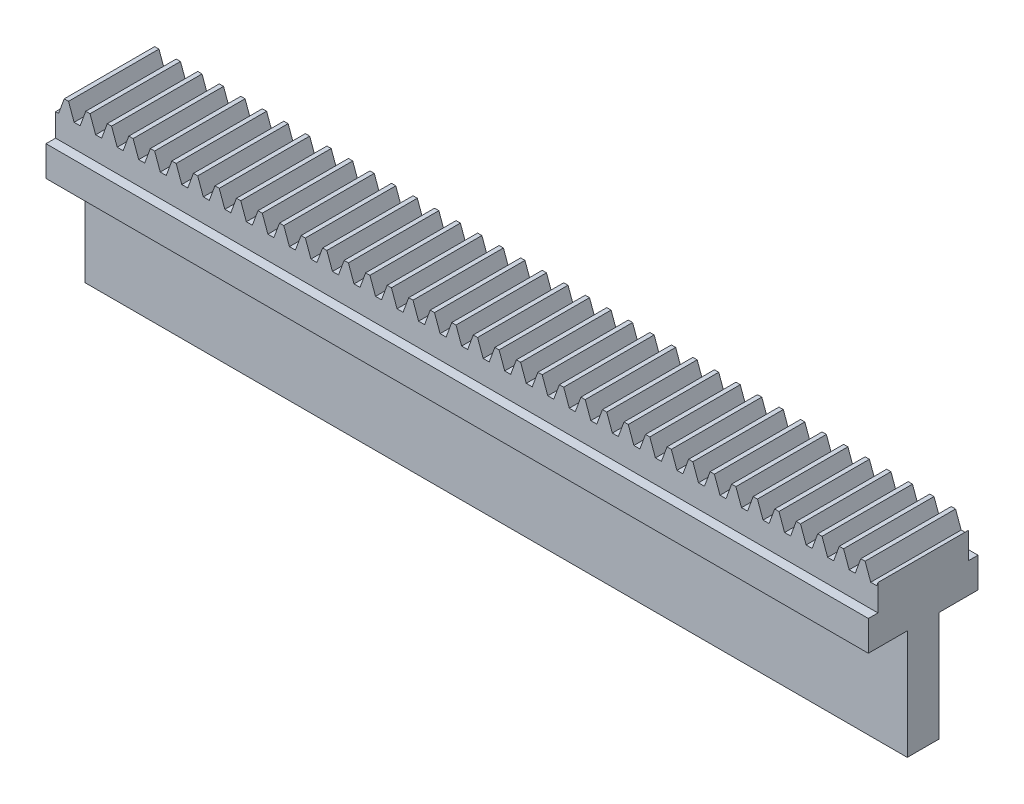
SolidWorks part; units mm, degrees
extrude "Blank" add sketch "BlankSke" against normal blind 20
sketch "BlankSke" plane through (0, 0, 0) normal (0, 0, 1) x (1, 0, 0)
  line L1 (0, 0) -> (150, 0)
  line L2 (0, 0) -> (0, 12.5)
  line L3 (0, 12.5) -> (150, 12.5)
  line L4 (150, 0) -> (150, 12.5)
  dimension "Length" = 150
ref_plane "Plane1" through (0, 0, 0) normal (0, 0, 1) x (1, 0, 0)
ref_plane "Plane2" through (0, 0, 0) normal (0, 1, 0) x (1, 0, 0)
ref_plane "Plane3" through (0, 0, 0) normal (1, 0, 0) x (0, 0, -1)
other "Configuration Table"
sketch "HoldingSke" plane through (0, 0, 0) normal (0, 1, 0) x (1, 0, 0)
  line L0 (0, 0) -> (0.1113, 0.7922)
  line L1 (-15, 0) -> (100, 0) construction
  line L2 (0, 0) -> (-2.1039, 2.3779)
  line L3 (0, 0) -> (-11.863, 4.5341)
  line L4 (0, 0) -> (6.6156, 5.5511)
  line L5 (0, 0) -> (-23.7986, -8.8762)
  line L6 (0, 0) -> (-10.5278, -7.1032)
  line L9 (-71.009, 38.7566) -> (69.9449, 90.0596)
  line L10 (-76.2, 3.6279) -> (-64.95, 3.6279)
  line L11 (0, 0) -> (-7, 0)
  line L12 (-76.2, 101.6) -> (-76.155, 101.6)
  line L13 (24.9733, 27.94) -> (52.9518, 28.4284)
  line L14 (24.9733, 27.94) -> (24.9743, 27.94)
  line L15 (24.9733, 27.94) -> (100.4006, 29.5858)
  circle A0 centre (0, 0) radius 19.05
  circle A1 centre (0, 0) radius 5.625
  circle A2 centre (0, 0) radius 12.7
  dimension "Num_teeth" = 40
  dimension "Width" = 7
  dimension "Length" = 150
  dimension "Pitch_height" = 11.25
sketch "TooCutSkeIll" plane through (0, 0, 0) normal (0, 0, 1) x (1, 0, 0)
  line L0 (-1.5597, 12.4671) -> (-0.6231, 9.8938)
  line L1 (-0.3285, 9.6875) -> (0.3285, 9.6875)
  line L2 (0.6231, 9.8938) -> (1.5597, 12.4671)
  line L3 (150, 12.5) -> (0, 12.5) construction
  line L4 (0, 0) -> (0, 64.897) construction
  line L5 (-13.208, 11.25) -> (12.954, 11.25) construction
  line L6 (0, 0) -> (150, 0) construction
  line L7 (1.1167, 11.25) -> (1.1167, 48.7463) construction
  line L8 (-1.1167, 11.25) -> (-1.1167, 48.7463) construction
  line L9 (1.6067, 12.5) -> (1.6067, 12.5254)
  line L10 (-1.6067, 12.5) -> (-1.6067, 12.5254)
  line L11 (-1.6067, 12.5254) -> (1.6067, 12.5254)
  arc A0 (0.3285, 9.6875) -> (0.6231, 9.8938) centre (0.3285, 10.001) ccw
  arc A1 (-0.6231, 9.8938) -> (-0.3285, 9.6875) centre (-0.3285, 10.001) ccw
  arc A2 (1.6067, 12.5) -> (1.5597, 12.4671) centre (1.6067, 12.45) ccw
  arc A3 (-1.5597, 12.4671) -> (-1.6067, 12.5) centre (-1.6067, 12.45) ccw
  dimension "Addendum_plus" = 1.2754
  dimension "Pitch_height" = 11.25
  dimension "Pressure_angle" = 20
  dimension "Gap_width" = 2.2335
  dimension "Dedendum" = 1.5625
extrude "ToothCutIll" [suppressed] cut sketch "TooCutSkeIll" against normal through all
sketch "TooCutSkeSim" plane through (0, 0, 0) normal (0, 0, 1) x (1, 0, 0)
  line L0 (0.548, 9.6875) -> (-0.548, 9.6875)
  line L1 (1.581, 12.5254) -> (0.548, 9.6875)
  line L2 (0, 17.4625) -> (0, 53.467) construction
  line L3 (1.581, 12.5254) -> (-1.581, 12.5254)
  line L6 (-1.581, 12.5254) -> (-0.548, 9.6875)
  line L9 (-1.1167, 11.25) -> (1.1167, 11.25) construction
  line L10 (0, 0) -> (150, 0) construction
  line L11 (1.1167, 11.25) -> (1.1167, 53.467) construction
  line L12 (-1.1167, 11.25) -> (-1.1167, 53.467) construction
  dimension "Addendum_plus" = 1.2754
  dimension "Pitch_height" = 11.25
  dimension "Pressure_angle" = 20
  dimension "Gap_width" = 2.2335
  dimension "Dedendum" = 1.5625
extrude "ToothCutSim" cut sketch "TooCutSkeSim" against normal through all
pattern_linear "TeethCuts" count 40 spacing 3.927 along (1, 0, 0) of "ToothCutIll", "ToothCutSim"
sketch "Croquis3" plane through (0, 0, 0) normal (0, 0, 1) x (1, 0, 0)
  line L0 (0, 9.6875) -> (0, 0) construction
  line L1 (0, 5.5) -> (150.5773, 5.5)
  line L2 (0, 5.5) -> (0, 12.8527)
  line L3 (0, 12.8527) -> (150.5773, 12.8527)
  line L4 (150.5773, 5.5) -> (150.5773, 12.8527)
  line L5 (123.408, 0) -> (123.408, 5.5) construction
  line L6 (0, 0) -> (150, 0) construction
  dimension "D1" = 5.5
extrude "Cortar-Extruir1" cut sketch "Croquis3" against normal blind 1.75
sketch "Croquis4" plane through (0, 0, -20) normal (0, 0, -1) x (-1, 0, 0)
  line L0 (-150, 0) -> (-150, 10.3093) construction
  line L1 (-150, 5.5) -> (0, 5.5)
  line L2 (-150, 5.5) -> (-150, 14.4015)
  line L3 (-150, 14.4015) -> (0, 14.4015)
  line L4 (0, 5.5) -> (0, 14.4015)
  line L5 (0, 0) -> (-150, 0) construction
  dimension "D1" = 5.5
extrude "Cortar-Extruir2" cut sketch "Croquis4" against normal blind 1.75
sketch "Croquis5" plane through (150, 0, 0) normal (1, 0, 0) x (0, 0, -1)
  line L0 (0, 0) -> (18.25, 10.3093) construction
  line L1 (18.25, 10.3093) -> (1.75, 10.3093) construction
  line L2 (1.75, 10.3093) -> (20, 0) construction
  circle A0 centre (10, 5.6489) radius 2
  dimension "D1" = 4
sketch "Croquis6" plane through (0, 0, 0) normal (0, -1, 0) x (1, 0, 0)
  line L6 (0, -20) -> (0, 0) construction
  line L8 (0, -7.1) -> (150, -7.1)
  line L9 (0, -7.1) -> (0, -12.9)
  line L11 (0, -12.9) -> (150, -12.9)
  line L12 (150, -7.1) -> (150, -12.9)
  line L13 (150, -20) -> (150, 0) construction
  line L14 (25.8218, 0) -> (25.8218, -7.1) construction
  line L15 (0, 0) -> (150, 0) construction
  line L16 (25.8218, -7.1) -> (32.7674, -12.9) construction
  line L17 (32.7674, -12.9) -> (32.7674, -20) construction
  line L18 (0, -20) -> (150, -20) construction
  dimension "D1" = 5.8
extrude "Saliente-Extruir1" add sketch "Croquis6" along normal blind 20
equation "' \"Module@HoldingSke\" = 6.35"
equation "' \"Num_teeth@HoldingSke\" = 12"
equation "' \"Ap@HoldingSke\" =  20"
equation "' \"Ap@HoldingSke\" = 20"
equation "' \"Width@HoldingSke\" = 0.25 * 25.4"
equation "' \"Show_teeth@HoldingSke\" = 500"
equation "' \"Backlash@HoldingSke\" = 0.009 * 25.4"
equation "' \"Addendum_fac@HoldingSke\" = 1.0"
equation "' \"Dedendum_fac@HoldingSke\" = 1.25"
equation "' \"Dedendum_add@HoldingSke\" = 0.00005 * 25.4"
equation "' \"Clearance_fac@HoldingSke\" = 0.25"
equation "' \"Pitch_height@HoldingSke\" = 1 * 25.4"
equation "' \"Length@HoldingSke\" = 4.71 * 25.4"
equation "\"Pitch@HoldingSke\" = 1 / \"Module@HoldingSke\""
equation "\"MPH@HoldingSke\" = \"Dedendum_fac@HoldingSke\" / \"Pitch@HoldingSke\" + 2 * \"Dedendum_add@HoldingSke\" + 0.002 * 25.4"
equation "\"MPH@HoldingSke\" = ((sgn( \"MPH@HoldingSke\" - \"Pitch_height@HoldingSke\")+1)*( \"MPH@HoldingSke\" - \"Pitch_height@HoldingSke\"))/2 + \"Pitch_height@HoldingSke\""
equation "\"Blank_height@BlankSke\" = \"Pitch_height@HoldingSke\" + \"Addendum_fac@HoldingSke\"  / \"Pitch@HoldingSke\" "
equation "\"Length@BlankSke\" =  \"Length@HoldingSke\""
equation "\"Pressure_angle@TooCutSkeIll\" = \"Ap@HoldingSke\""
equation "\"Addendum_plus@TooCutSkeIll\" =  \"Addendum_fac@HoldingSke\"  / \"Pitch@HoldingSke\" + 0.001 *25.4"
equation "\"Dedendum@TooCutSkeIll\" = \"Dedendum_fac@HoldingSke\"  / \"Pitch@HoldingSke\""
equation "\"Pitch_height@TooCutSkeIll\" =  \"MPH@HoldingSke\""
equation "\"Gap_width@TooCutSkeIll\" = 3.14159265 / 2 / \"Pitch@HoldingSke\" + 6 * \"Backlash@HoldingSke\""
equation "\"Pressure_angle@TooCutSkeSim\" = \"Ap@HoldingSke\""
equation "\"Addendum_plus@TooCutSkeSim\" =  \"Addendum_fac@HoldingSke\"  / \"Pitch@HoldingSke\" + 0.001 * 25.4"
equation "\"Dedendum@TooCutSkeSim\" = \"Dedendum_fac@HoldingSke\"  / \"Pitch@HoldingSke\""
equation "\"Pitch_height@TooCutSkeSim\" =  \"MPH@HoldingSke\""
equation "\"Gap_width@TooCutSkeSim\" = 3.14159265 / 2 / \"Pitch@HoldingSke\" + 6 * \"Backlash@HoldingSke\""
equation "\"Root_fillet@TooCutSkeIll\" = \"Clearance_fac@HoldingSke\" / \"Pitch@HoldingSke\" + \"Dedendum_add@HoldingSke\""
equation "\"Break_rad@TooCutSkeIll\" = 0.02 / \"Pitch@HoldingSke\" * 2"
equation "\"Linear_pitch@TeethCuts\" = 3.14159265 / \"Pitch@HoldingSke\""
equation "\"Num_teeth@HoldingSke\" = int( ( \"Length@HoldingSke\" + 0 ) / (3.14159265 / \"Pitch@HoldingSke\")) + 0.9999  + 1"
equation " \"Num_teeth@TeethCuts\" = int( \"Show_teeth@HoldingSke\" ) + 1"
equation " \"Num_teeth@TeethCuts\" = ((sgn( \"Num_teeth@TeethCuts\" - \"Num_teeth@HoldingSke\" )-1)*( \"Num_teeth@TeethCuts\" - \"Num_teeth@HoldingSke\" ))/-2+ \"Num_teeth@HoldingSke\""
equation " \"Num_teeth@TeethCuts\" = ((sgn( \"Num_teeth@TeethCuts\" - 2.0)+1)*( \"Num_teeth@TeethCuts\" - 2.0))/2 +2.0"
